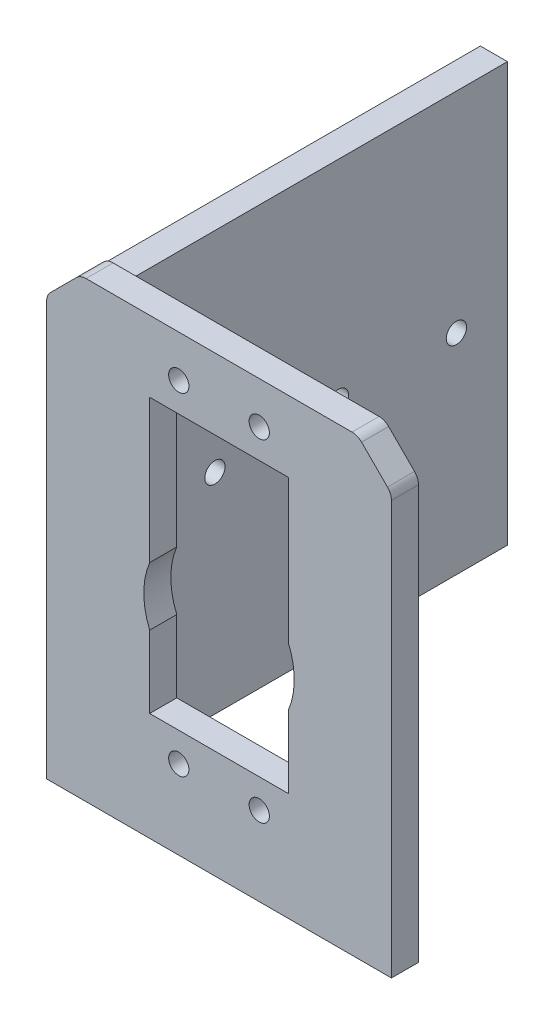
SolidWorks part; units mm, degrees
ref_plane "Front Plane" through (0, 0, 0) normal (0, 0, 1) x (1, 0, 0)
ref_plane "Top Plane" through (0, 0, 0) normal (0, 1, 0) x (1, 0, 0)
ref_plane "Right Plane" through (0, 0, 0) normal (1, 0, 0) x (0, 0, -1)
sketch "Sketch1" plane through (0, 0, 0) normal (0, 0, 1) x (1, 0, 0)
  line L12 (0, 61.1716) -> (0, 0)
  line L13 (0, 0) -> (51, 0)
  line L14 (51, 0) -> (51, 61.1716)
  line L15 (50.4142, 62.5858) -> (46.5858, 66.4142)
  line L16 (45.1716, 67) -> (5.8284, 67)
  line L17 (4.4142, 66.4142) -> (0.5858, 62.5858)
  line L18 (15.25, 56.5) -> (35.75, 56.5)
  line L19 (15.25, 16) -> (15.25, 26.6753)
  line L20 (15.25, 35.3247) -> (15.25, 56.5)
  line L21 (35.75, 56.5) -> (35.75, 35.3247)
  line L22 (35.75, 26.6753) -> (35.75, 16)
  line L23 (35.75, 16) -> (15.25, 16)
  arc A8 (51, 61.1716) -> (50.4142, 62.5858) centre (49, 61.1716) ccw
  arc A9 (46.5858, 66.4142) -> (45.1716, 67) centre (45.1716, 65) ccw
  arc A10 (5.8284, 67) -> (4.4142, 66.4142) centre (5.8284, 65) ccw
  arc A11 (0.5858, 62.5858) -> (0, 61.1716) centre (2, 61.1716) ccw
  arc A14 (15.25, 35.3247) -> (15.25, 26.6753) centre (25.5, 31) ccw
  arc A15 (35.75, 26.6753) -> (35.75, 35.3247) centre (25.5, 31) ccw
  circle A16 centre (19.55, 11.7) radius 1.5
  circle A17 centre (31.45, 11.7) radius 1.5
  circle A18 centre (31.45, 60.8) radius 1.5
  circle A19 centre (19.55, 60.8) radius 1.5
extrude "Boss-Extrude3" add sketch "Sketch1" along normal blind 4
sketch "Sketch2" plane through (0, 0, 0) normal (0, 0, -1) x (-1, 0, 0)
  line L0 (0, 0) -> (-51, 0) construction
  line L1 (-0.1522, 61.9369) -> (-4.1522, 61.9369)
  line L2 (-0.1522, 61.9369) -> (-0.1522, 0)
  line L3 (-0.1522, 0) -> (-4.1522, 0)
  line L4 (-4.1522, 61.9369) -> (-4.1522, 0)
  arc A0 (0, 61.1716) -> (-0.5858, 62.5858) centre (-2, 61.1716) ccw construction
extrude "Boss-Extrude4" add sketch "Sketch2" along normal blind 60
sketch "Sketch3" plane through (0.1522, 0, 0) normal (-1, 0, 0) x (0, 0, 1)
  line L0 (0, 30.9685) -> (-60, 30.9685) construction
  line L1 (0, 0) -> (0, 61.9369) construction
  line L2 (-60, 0) -> (-60, 61.9369) construction
  circle A0 centre (-52.4526, 30.9685) radius 1.5
  circle A1 centre (-35.0041, 30.9685) radius 1.5
  circle A2 centre (-16.7419, 30.9685) radius 1.5
extrude "Cut-Extrude1" cut sketch "Sketch3" against normal blind 10 contours A2 | A1 | A0
